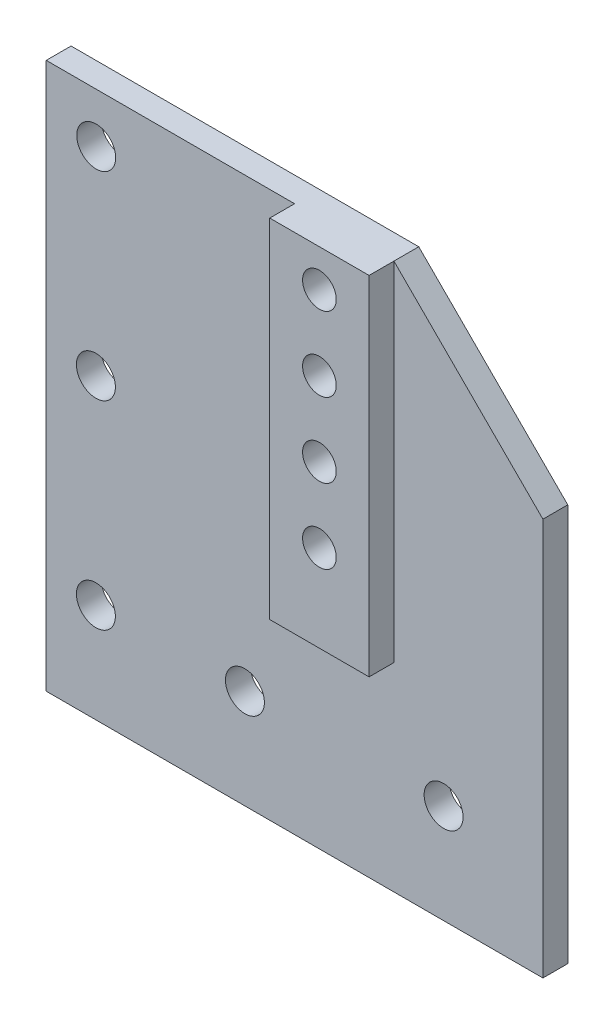
SolidWorks part; units mm, degrees
ref_plane "Front Plane" through (0, 0, 0) normal (0, 0, 1) x (1, 0, 0)
ref_plane "Top Plane" through (0, 0, 0) normal (0, 1, 0) x (1, 0, 0)
ref_plane "Right Plane" through (0, 0, 0) normal (1, 0, 0) x (0, 0, -1)
sketch "Sketch1" plane through (0, 0, 0) normal (0, 0, 1) x (1, 0, 0)
  line L0 (-254, -12.7) -> (-266.7, -12.7)
  line L2 (-266.7, 57.15) -> (-254, 57.15)
  line L3 (-254, -16.7024) -> (-254, 609.6) construction
  line L4 (-254, -12.7) -> (-203.2, -12.7)
  line L5 (-254, 57.15) -> (-222.25, 57.15)
  line L6 (-203.2, -12.7) -> (-203.2, 12.7)
  line L7 (-254, 12.7) -> (254, 12.7) construction
  line L13 (-222.25, 57.15) -> (-203.2, 38.1)
  line L15 (-266.7, -12.7) -> (-266.7, 57.15)
  line L16 (-266.7, 609.6) -> (-266.7, -16.7024) construction
  line L17 (-203.2, 12.7) -> (-203.2, 38.1)
  dimension "D1" = 69.85
  dimension "D2" = 25.4
  dimension "D3" = 31.75
extrude "Boss-Extrude1" add sketch "Sketch1" along normal blind 3.175
sketch "Sketch2" plane through (0, 0, 3.175) normal (0, 0, 1) x (1, 0, 0)
  line L0 (-203.2, -12.7) -> (-203.2, 12.7) construction
  line L1 (-215.9, 0) -> (-241.3, 0) construction
  line L2 (-203.2, 0) -> (-215.9, 0) construction
  line L3 (-254, -12.7) -> (-266.7, -12.7) construction
  line L4 (-260.35, -12.7) -> (-260.35, 0) construction
  line L5 (-260.35, 0) -> (-260.35, 25.4) construction
  line L6 (-260.35, 25.4) -> (-260.3118, 50.7989) construction
  line L7 (-260.3118, 25.4) -> (-260.3118, 51.0017) construction
  line L8 (-254, 12.7) -> (254, 12.7) construction
  dimension "D1" = 12.7
  dimension "D2" = 25.4
  dimension "D3" = 12.7
  dimension "D4" = 25.4
  dimension "D5" = 25.3989
hole_wizard "#10 Clearance Hole1" positions "Sketch3" profile "Sketch4" hole size "#10" standard "ANSI Inch" end condition through all
sketch "Sketch3" plane through (0, 0, 3.175) normal (0, 0, 1) x (1, 0, 0)
  point P15 (-260.3118, 50.7989)
  point P18 (-260.35, 25.4)
  point P21 (-260.35, 0)
  point P24 (-241.3, 0)
  point P27 (-215.9, 0)
sketch "Sketch4" plane through (-260.3118, 50.7989, 3.175) normal (1, 0, 0) x (0, -1, 0)
  line L0 (0, 0) -> (0, 3.175)
  line L1 (0, 3.175) -> (2.4892, 3.175)
  line L2 (2.4892, 3.175) -> (2.4892, 0)
  line L5 (2.4892, 0) -> (0, 0)
  line L11 (0, -6.35) -> (0, 107.95) construction
  dimension "Thru Hole Dia." = 4.9784
  dimension "Thru Hole Depth" = 3.175
sketch "Sketch5" plane through (0, 0, 3.175) normal (0, 0, 1) x (1, 0, 0)
  line L0 (-222.25, 57.15) -> (-222.25, 50.8) construction
  line L1 (-222.25, 57.15) -> (-234.95, 57.15)
  line L3 (-234.95, 57.15) -> (-234.95, 12.7)
  line L4 (-222.25, 50.8) -> (-222.25, 12.7)
  line L5 (-222.25, 12.7) -> (-234.95, 12.7)
  line L6 (-222.25, 50.8) -> (-222.25, 57.15)
  line L7 (-222.25, 57.15) -> (-266.7, 57.15) construction
  point P7 (-222.25, 50.8)
  dimension "D3" = 38.1
extrude "Boss-Extrude2" add sketch "Sketch5" along normal blind 3.175
sketch "Sketch6" plane through (0, 0, 6.35) normal (0, 0, 1) x (1, 0, 0)
  line L0 (-228.6, 57.15) -> (-228.6, 52.3875) construction
  line L1 (-228.6, 52.3875) -> (-228.6, 42.8625) construction
  line L2 (-228.6, 42.8625) -> (-228.6, 33.3375) construction
  line L3 (-222.25, 57.15) -> (-234.95, 57.15) construction
  line L4 (-228.6, 33.3375) -> (-228.6, 23.8125) construction
  dimension "D1" = 9.525
  dimension "D2" = 4.7625
  dimension "D3" = 9.525
  dimension "D4" = 9.525
hole_wizard "#8 Clearance Hole1" positions "Sketch7" profile "Sketch8" hole size "#8" standard "ANSI Inch" end condition through all
sketch "Sketch7" plane through (0, 0, 6.35) normal (0, 0, 1) x (1, 0, 0)
  point P0 (-228.6, 42.8625)
  point P3 (-228.6, 52.3875)
  point P7 (-228.6, 33.3375)
  point P10 (-228.6, 23.8125)
sketch "Sketch8" plane through (-228.6, 42.8625, 6.35) normal (1, 0, 0) x (0, -1, 0)
  line L0 (0, 0) -> (0, 6.35)
  line L1 (0, 6.35) -> (2.1526, 6.35)
  line L2 (2.1526, 6.35) -> (2.1526, 0)
  line L5 (2.1526, 0) -> (0, 0)
  line L11 (0, -6.35) -> (0, 107.95) construction
  dimension "Thru Hole Dia." = 4.3053
  dimension "Thru Hole Depth" = 6.35
